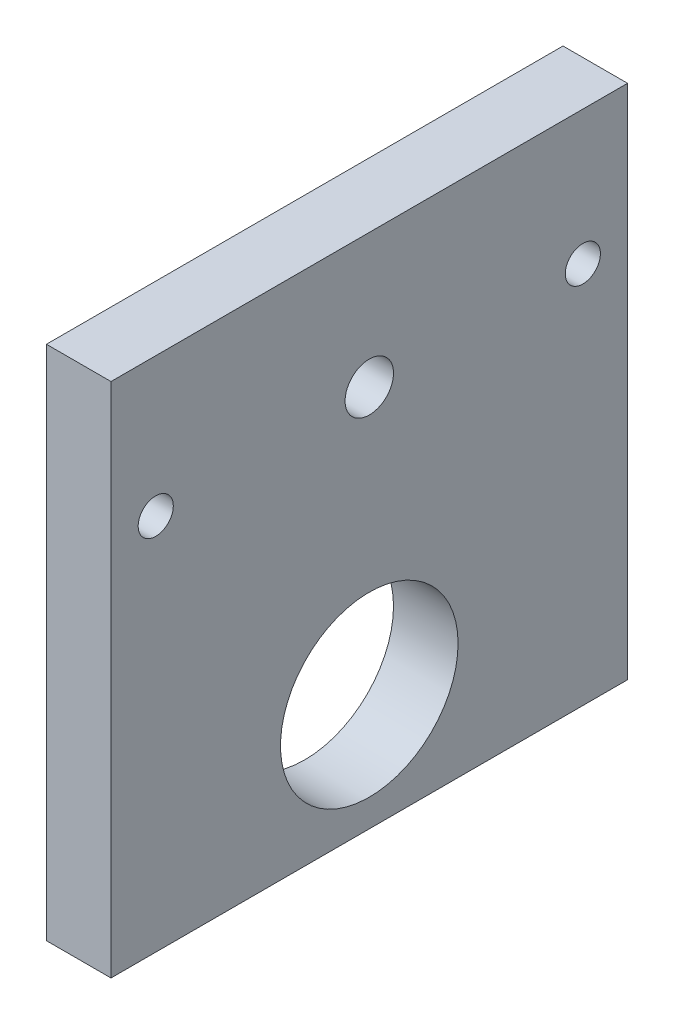
SolidWorks part; units mm, degrees
ref_plane "Front Plane" through (0, 0, 0) normal (0, 0, 1) x (1, 0, 0)
ref_plane "Top Plane" through (0, 0, 0) normal (0, 1, 0) x (1, 0, 0)
ref_plane "Right Plane" through (0, 0, 0) normal (1, 0, 0) x (0, 0, -1)
sketch "Sketch1" plane through (0, 0, 0) normal (1, 0, 0) x (0, 0, -1)
  line L1 (-25.4, -25.4) -> (25.4, -25.4)
  line L2 (-25.4, -25.4) -> (-25.4, 25.4)
  line L3 (-25.4, 25.4) -> (25.4, 25.4)
  line L4 (25.4, -25.4) -> (25.4, 25.4)
  line L5 (-25.4, -25.4) -> (25.4, 25.4) construction
  line L6 (-25.4, 25.4) -> (25.4, -25.4) construction
  point P0 (0, 0)
  dimension "D1" = 50.8
  dimension "D2" = 50.8
extrude "Boss-Extrude1" add sketch "Sketch1" along normal blind 6.35
hole_wizard "11/16 (0.6875) Diameter Hole1" positions "Sketch9" profile "Sketch8" hole size "11/16" standard "ANSI Inch"
sketch "Sketch9" plane through (6.35, 0, 0) normal (1, 0, 0) x (0, 0, -1)
  line L0 (-25.4, -25.4) -> (25.4, -25.4) construction
  point P0 (0, -13.97)
  dimension "D1" = 11.43
sketch "Sketch8" plane through (6.35, -13.97, 0) normal (0, 1, 0) x (0, 0, -1)
  line L0 (0, 0) -> (0, 75.3503)
  line L1 (0, 75.3503) -> (8.7312, 70.104)
  line L2 (8.7312, 70.104) -> (8.7312, 0)
  line L5 (8.7312, 0) -> (0, 0)
  line L10 (0, 75.3503) -> (-8.7313, 70.104) construction
  line L11 (0, -6.35) -> (0, 107.95) construction
  dimension "Hole Dia." = 17.4625
  dimension "Hole Depth" = 70.104
  dimension "Drill Angle" = 118
hole_wizard "3/16 (0.1875) Diameter Hole1" positions "Sketch3" profile "Sketch2" hole size "3/16" standard "ANSI Inch"
sketch "Sketch3" plane through (6.35, 0, 0) normal (1, 0, 0) x (0, 0, -1)
  circle A0 centre (0, -13.97) radius 8.7312 construction
  point P0 (0, 12.2301)
  dimension "D1" = 26.2001
  dimension "D2" = 0
sketch "Sketch2" plane through (6.35, 12.2301, 0) normal (0, 1, 0) x (0, 0, -1)
  line L0 (0, 0) -> (0, 71.5348)
  line L1 (0, 71.5348) -> (2.3812, 70.104)
  line L2 (2.3812, 70.104) -> (2.3812, 0)
  line L5 (2.3812, 0) -> (0, 0)
  line L10 (0, 71.5348) -> (-2.3813, 70.104) construction
  line L11 (0, -6.35) -> (0, 107.95) construction
  dimension "Hole Dia." = 4.7625
  dimension "Hole Depth" = 70.104
  dimension "Drill Angle" = 118
hole_wizard "#29 (0.136) Diameter Hole1" positions "Sketch5" profile "Sketch4" hole size "#29" standard "ANSI Inch"
sketch "Sketch5" plane through (6.35, 0, 0) normal (1, 0, 0) x (0, 0, -1)
  circle A0 centre (0, 12.2301) radius 2.3812 construction
  point P0 (21, 12.2301)
  point P2 (-21, 11.7415)
  dimension "D1" = 0.4886
  dimension "D2" = 0
  dimension "D3" = 21
  dimension "D4" = 42
sketch "Sketch4" plane through (6.35, 12.2301, -21) normal (0, 1, 0) x (0, 0, -1)
  line L0 (0, 0) -> (0, 71.1418)
  line L1 (0, 71.1418) -> (1.7272, 70.104)
  line L2 (1.7272, 70.104) -> (1.7272, 0)
  line L5 (1.7272, 0) -> (0, 0)
  line L10 (0, 71.1418) -> (-1.7272, 70.104) construction
  line L11 (0, -6.35) -> (0, 107.95) construction
  dimension "Hole Dia." = 3.4544
  dimension "Hole Depth" = 70.104
  dimension "Drill Angle" = 118
hole_wizard "#10-32 Tapped Hole1" positions "Sketch11" profile "Sketch10" tap size "#10-32" standard "ANSI Inch"
sketch "Sketch11" plane through (0, -25.4, 0) normal (0, -1, 0) x (-1, 0, 0)
  line L0 (-6.35, 25.4) -> (0, 25.4) construction
  line L1 (-6.35, 25.4) -> (0, 25.4) construction
  line L2 (-6.35, -25.4) -> (0, -25.4) construction
  point P0 (-3.175, -19.05)
  point P2 (-3.175, 19.05)
  point P6 (-3.175, 25.4)
  dimension "D1" = 0
  dimension "D2" = 0
  dimension "D3" = 6.35
  dimension "D4" = 6.35
sketch "Sketch10" plane through (3.175, -25.4, 19.05) normal (1, 0, 0) x (0, 0, -1)
  line L0 (0, 0) -> (0, 13.1513)
  line L1 (0, 13.1513) -> (2.0193, 11.938)
  line L2 (2.0193, 11.938) -> (2.0193, 0)
  line L5 (2.0193, 0) -> (0, 0)
  line L10 (0, 13.1513) -> (-2.0193, 11.938) construction
  line L11 (0, -6.35) -> (0, 107.95) construction
  dimension "Tap Drill Dia." = 4.0386
  dimension "Tap Drill Depth" = 11.938
  dimension "Drill Angle" = 118
cosmetic thread "Hole Thread1"
cosmetic thread "Hole Thread2"
